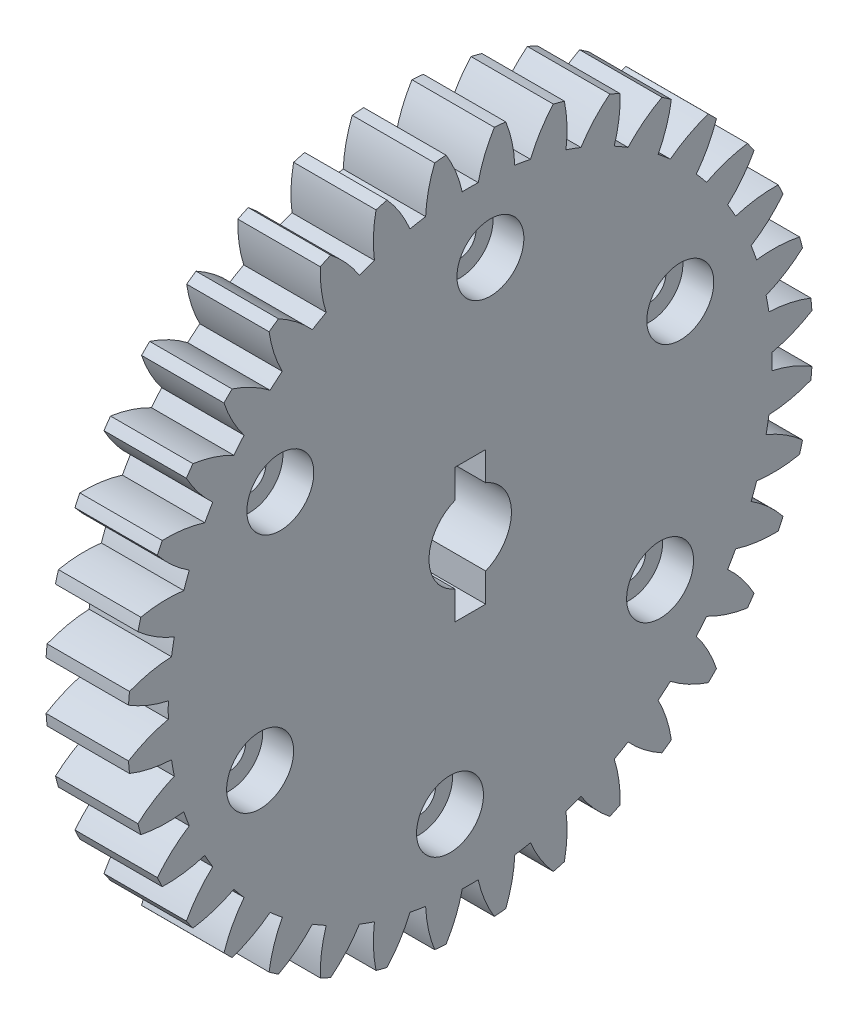
SolidWorks part; units mm, degrees
material "PLA personnalisé"
ref_plane "Plane1" through (0, 0, 0) normal (0, 0, 1) x (1, 0, 0)
ref_plane "Plane2" through (0, 0, 0) normal (0, 1, 0) x (1, 0, 0)
ref_plane "Plane3" through (0, 0, 0) normal (1, 0, 0) x (0, 0, -1)
other "Configuration Table"
sketch "HoldingSke" plane through (0, 0, 0) normal (0, 1, 0) x (1, 0, 0)
  line L0 (0, 0) -> (0.4623, -0.3359)
  line L1 (-15, 0) -> (100, 0) construction
  line L2 (0, 0) -> (-2.1039, 2.3779)
  line L3 (0, 0) -> (-11.863, 4.5341)
  line L4 (0, 0) -> (6.9867, 5.0761)
  line L5 (0, 0) -> (-46.8476, -17.4728)
  line L6 (0, 0) -> (-6.6317, -4.4744)
  line L7 (-2.1039, 2.3779) -> (8.6586, 51.2059)
  line L8 (-76.2, 54.61) -> (-74.8, 54.61)
  line L9 (-71.009, 38.7566) -> (-53.1078, 45.2721)
  line L10 (-76.2, 71.12) -> (104.1128, 71.12)
  line L11 (0, 0) -> (-8, 0)
  line L12 (-76.2, 101.6) -> (-76.147, 101.6)
  line L13 (24.9733, 27.94) -> (52.9518, 28.4284)
  line L14 (24.9733, 27.94) -> (24.9743, 27.94)
  line L15 (24.9733, 27.94) -> (100.4006, 29.5858)
  line L16 (-63.627, -1.75) -> (-12.827, -1.75)
  circle A0 centre (0, 0) radius 4
  circle A1 centre (0, 0) radius 29.3115
  circle A2 centre (0, 0) radius 37.5
  circle A3 centre (0, 0) radius 4
  dimension "MHD" = 58.623
  dimension "Hub_dia" = 75
  dimension "Bore" = 8
  dimension "MBD" = 8
  dimension "Num_teeth" = 36
  dimension "Pitch" = 0.5714
  dimension "Overall_len" = 50
  dimension "Show_teeth" = 36
  dimension "Thickness" = 8
  dimension "OAL" = 50.0001
  dimension "T_dim" = 1.4
  dimension "Ap" = 20
  dimension "H" = 19.05
  dimension "Pitch_radius" = 180.3128
  dimension "Width" = 8
  dimension "Backlash" = 0.053
  dimension "Addendum_fac" = 1
  dimension "Dedendum_fac" = 1.25
  dimension "Clearance_fac" = 0.25
  dimension "Dedendum_add" = 0.001
  dimension "Module" = 1.75
sketch "BasProSke" plane through (0, 0, 0) normal (0, 1, 0) x (1, 0, 0)
  line L0 (-10, 0) -> (60, 0) construction
  line L1 (0, 0) -> (0, 33.25)
  line L2 (0, 0) -> (8, 0)
  line L3 (8, 0) -> (8, 33.25)
  line L4 (8, 33.25) -> (0, 33.25)
  dimension "Thickness" = 8
  dimension "Diameter" = 66.5
revolve "Base-Revolve" add sketch "BasProSke" angle 360 about L0
sketch "TooCutSke" plane through (0, 0, 0) normal (1, 0, 0) x (0, 0, -1)
  line L1 (0, 0) -> (0, 107) construction
  line L2 (0, 0) -> (-1.4667, 31.4658) construction
  line L3 (0, 0) -> (-5.4863, 62.7083) construction
  line L4 (-1.4667, 31.4658) -> (-2.7431, 31.3542) construction
  arc A0 (0.7738, 29.3013) -> (-0.7738, 29.3013) centre (0, 0) ccw
  arc A1 (2.3593, 33.1917) -> (-2.3593, 33.1917) centre (0, 0) ccw
  circle A2 centre (0, 0) radius 31.5 construction
  circle A3 centre (0, 0) radius 29.6003 construction
  arc A4 (-0.7738, 29.3013) -> (-2.3593, 33.1917) centre (-13.0715, 26.5578) ccw
  arc A5 (2.3593, 33.1917) -> (0.7738, 29.3013) centre (13.0715, 26.5578) ccw
  dimension "Root_dia" = 58.623
  dimension "Overcut_dia" = 66.5508
  dimension "Pitch_dia" = 63
  dimension "Base_dia" = 59.2006
  dimension "Flank_rad" = 12.6
  dimension "Half_ang" = 5
  dimension "Half_CT" = 1.2813
extrude "ToothCut" cut sketch "TooCutSke" along normal through all
fillet "Breaks" [suppressed] radius 0.035 tangent propagation no
fillet "RootFillets" [suppressed] radius 0.4385
pattern_circular "TeethCuts" count 36 every 10 about axis through (-10, 0, 0) along (1, 0, 0) of "ToothCut", "RootFillets", "Breaks"
sketch "HubNeaOneSke" plane through (0, 0, 0) normal (-1, 0, 0) x (0, 0, 1)
  circle A0 centre (0, 0) radius 29.3115
  dimension "Diameter" = 58.623
extrude "HubNearOne" [suppressed] add sketch "HubNeaOneSke" along normal blind 42.0001
sketch "HubNeaBotSke" plane through (0, 0, 0) normal (-1, 0, 0) x (0, 0, 1)
  circle A0 centre (0, 0) radius 29.3115
  dimension "Diameter" = 58.623
extrude "HubNearBoth" [suppressed] add sketch "HubNeaBotSke" along normal blind 21
ref_plane "FarPln" through (8, 0, 0) normal (1, 0, 0) x (0, 0, -1)
sketch "HubFarSke" plane through (8, 0, 0) normal (1, 0, 0) x (0, 0, -1)
  circle A0 centre (0, 0) radius 29.3115
  dimension "Diameter" = 58.623
extrude "HubFar" [suppressed] add sketch "HubFarSke" along normal blind 21
sketch "BorSke" plane through (0, 0, 0) normal (1, 0, 0) x (0, 0, -1)
  circle A0 centre (0, 0) radius 4
  dimension "Diameter" = 8
extrude "Bore" cut sketch "BorSke" along normal mid plane 100.0001
sketch "KeySke" plane through (0, 0, 0) normal (1, 0, 0) x (0, 0, -1)
  line L0 (-1.5, 0) -> (-1.5, 5.4)
  line L1 (-1.5, 5.4) -> (1.5, 5.4)
  line L2 (1.5, 5.4) -> (1.5, 0)
  line L3 (0, 0) -> (0, 34) construction
  line L4 (-1.5, 0) -> (1.5, 0)
  dimension "Offset" = 5.4
  dimension "Width" = 3
extrude "Keyway" [suppressed] cut sketch "KeySke" along normal mid plane 100.0001
pattern_circular "Keyway2" [suppressed] count 2 every 90 about axis through (-10, 0, 0) along (1, 0, 0) reverse direction yes
sketch "Esquisse2" plane through (8, 0, 0) normal (1, 0, 0) x (0, 0, -1)
  line L0 (2.8979, 33.1235) -> (0, 0) construction
  line L1 (1.3673, 15.6288) -> (2.5547, 29.2)
  arc A0 (3.4508, 33.0704) -> (2.3442, 33.1673) centre (0, 0) ccw construction
  circle A1 centre (0, 0) radius 29.3115
  circle A2 centre (0, 0) radius 15.6885
  circle A3 centre (1.961, 22.4144) radius 1.6
  circle A4 centre (0, 0) radius 22.5
  dimension "D1" = 3.2
  dimension "D2" = 45
extrude "Enlèv. mat.-Extru.2" cut sketch "Esquisse2" against normal blind 10 contours A3
sketch "Esquisse3" plane through (8, 0, 0) normal (1, 0, 0) x (0, 0, -1)
  circle A0 centre (1.961, 22.4144) radius 3.25
  dimension "D1" = 6.5
extrude "Enlèv. mat.-Extru.3" cut sketch "Esquisse3" against normal blind 3
pattern_circular "Répétition circulaire1" count 6 over 360 about axis through (50.0001, 0, 0) along (-1, 0, 0) of "Enlèv. mat.-Extru.2", "Enlèv. mat.-Extru.3"
sketch "Esquisse4" plane through (8, 0, 0) normal (1, 0, 0) x (0, 0, -1)
  line L1 (1.5, -6.5) -> (-1.5, -6.5)
  line L2 (1.5, -6.5) -> (1.5, 6.5)
  line L3 (1.5, 6.5) -> (-1.5, 6.5)
  line L4 (-1.5, -6.5) -> (-1.5, 6.5)
  line L5 (1.5, -6.5) -> (-1.5, 6.5) construction
  line L6 (1.5, 6.5) -> (-1.5, -6.5) construction
  point P0 (0, 0)
  dimension "D1" = 13
  dimension "D2" = 3
extrude "Enlèv. mat.-Extru.4" cut sketch "Esquisse4" against normal blind 10
equation "' \"Module@HoldingSke\" = 6.35"
equation "' \"Num_teeth@HoldingSke\" = 12"
equation "' \"Ap@HoldingSke\" =  20"
equation "' \"Ap@HoldingSke\" = 20"
equation "' \"Width@HoldingSke\" = 0.5 * 25.4"
equation "' \"Hub_dia@HoldingSke\"= 1 * 25.4"
equation "' \"Hub_dia@HoldingSke\" = 1 * 25.4"
equation "' \"Overall_len@HoldingSke\" = 1.0 * 25.4"
equation "' \"Bore@HoldingSke\" = 0.75 * 25.4"
equation "' \"T_dim@HoldingSke\" = 0.1 * 25.4"
equation "' \"Width@KeySke\" = 0.25 * 25.4"
equation "' \"Show_teeth@HoldingSke\" = 13"
equation "' \"Backlash@HoldingSke\" = 0.009 * 25.4"
equation "' \"Addendum_fac@HoldingSke\" = 1.0"
equation "' \"Dedendum_fac@HoldingSke\" = 1.25"
equation "' \"Dedendum_add@HoldingSke\" = 0.00005 * 25.4"
equation "' \"Clearance_fac@HoldingSke\" = 0.25"
equation "\"Pitch@HoldingSke\" = 1 / \"Module@HoldingSke\""
equation "\"Overcut_dia@TooCutSke\" = (\"Num_teeth@HoldingSke\" + 2 * \"Addendum_fac@HoldingSke\") / \"Pitch@HoldingSke\" + 0.002 * 25.4"
equation "\"Pitch_dia@TooCutSke\" = \"Num_teeth@HoldingSke\" / \"Pitch@HoldingSke\""
equation "\"Base_dia@TooCutSke\" = \"Num_teeth@HoldingSke\" / \"Pitch@HoldingSke\" * cos((\"Ap@HoldingSke\"  * 3.14159265 / 180))"
equation "\"Root_dia@TooCutSke\" = (\"Num_teeth@HoldingSke\" + 2) / \"Pitch@HoldingSke\" - 2 * (\"Addendum_fac@HoldingSke\" + \"Dedendum_fac@HoldingSke\") / \"Pitch@HoldingSke\" - \"Dedendum_add@HoldingSke\" * 2"
equation "\"Half_ang@TooCutSke\" = 180 / \"Num_teeth@HoldingSke\""
equation "\"Half_CT@TooCutSke\" = \"Num_teeth@HoldingSke\" / \"Pitch@HoldingSke\" * sin((3.14159265 / 2 / \"Num_teeth@HoldingSke\")) / 2 - 7 * \"Backlash@HoldingSke\" / 4"
equation "\"Flank_rad@TooCutSke\" = \"Num_teeth@HoldingSke\" / \"Pitch@HoldingSke\" / 5"
equation "\"Radius@RootFillets\" = \"Clearance_fac@HoldingSke\" / \"Pitch@HoldingSke\" + \"Dedendum_add@HoldingSke\""
equation "\"Break_rad@Breaks\" = 0.02 / \"Pitch@HoldingSke\""
equation "\"Thickness@HoldingSke\" = \"Width@HoldingSke\""
equation "\"OAL@HoldingSke\" = \"Thickness@HoldingSke\""
equation "\"MHD@HoldingSke\" = (\"Num_teeth@HoldingSke\" + 2) / \"Pitch@HoldingSke\" - 2 * (\"Addendum_fac@HoldingSke\" + \"Dedendum_fac@HoldingSke\")  / \"Pitch@HoldingSke\" - \"Dedendum_add@HoldingSke\" * 2"
equation "\"MBD@HoldingSke\" = (\"Num_teeth@HoldingSke\" + 2) / \"Pitch@HoldingSke\" - 2 * (\"Addendum_fac@HoldingSke\" + \"Dedendum_fac@HoldingSke\")  / \"Pitch@HoldingSke\" - \"Dedendum_add@HoldingSke\" * 2 - 0.002 * 25.4"
equation "\"MHD@HoldingSke\" = ((sgn( \"MHD@HoldingSke\" - \"Hub_dia@HoldingSke\" )-1)*( \"MHD@HoldingSke\" - \"Hub_dia@HoldingSke\" ))/-2+ \"Hub_dia@HoldingSke\""
equation "\"MBD@HoldingSke\" = ((sgn( \"MBD@HoldingSke\" - \"Bore@HoldingSke\" )-1)*( \"MBD@HoldingSke\" - \"Bore@HoldingSke\" ))/-2+ \"Bore@HoldingSke\""
equation "\"OAL@HoldingSke\" = ((sgn( \"OAL@HoldingSke\" - \"Overall_len@HoldingSke\" )+1)*( \"OAL@HoldingSke\" - \"Overall_len@HoldingSke\" ))/2 + \"Overall_len@HoldingSke\" + 0.000002 * 25.4"
equation "\"Num_teeth@TeethCuts\" = int( \"Show_teeth@HoldingSke\" ) + 1"
equation "\"Num_teeth@TeethCuts\" = ((sgn( \"Num_teeth@TeethCuts\" - \"Num_teeth@HoldingSke\" )-1)*( \"Num_teeth@TeethCuts\" - \"Num_teeth@HoldingSke\" ))/-2+ \"Num_teeth@HoldingSke\""
equation "\"Num_teeth@TeethCuts\" = ((sgn( \"Num_teeth@TeethCuts\" - 2.0)+1)*( \"Num_teeth@TeethCuts\" - 2.0))/2 +2.0"
equation "\"Angle@TeethCuts\" = 360.0 / \"Num_teeth@HoldingSke\""
equation "\"Diameter@BasProSke\" = (\"Num_teeth@HoldingSke\" + 2 * \"Addendum_fac@HoldingSke\") / \"Pitch@HoldingSke\""
equation "\"Thickness@BasProSke\"  = \"Thickness@HoldingSke\""
equation "' \"Fillet_rad@BasProSke\" =  \"Thickness@HoldingSke\" * 0.05"
equation "' \"Fillet_rad@BasProSke\" = \"Thickness@HoldingSke\" * 0.05"
equation "\"MHD@HoldingSke\" = ((sgn( \"MHD@HoldingSke\" - \"Root_dia@TooCutSke\" )-1)*( \"MHD@HoldingSke\" - \"Root_dia@TooCutSke\" ))/-2+ \"Root_dia@TooCutSke\""
equation "\"Diameter@HubNeaOneSke\" = \"MHD@HoldingSke\""
equation "\"Length@HubNearOne\" = \"OAL@HoldingSke\" - \"Thickness@BasProSke\""
equation "\"Diameter@HubNeaBotSke\" = \"MHD@HoldingSke\""
equation "\"Length@HubNearBoth\" = ( \"OAL@HoldingSke\" - \"Thickness@BasProSke\" ) / 2.0"
equation "\"Thickness@FarPln\" = \"Thickness@BasProSke\""
equation "\"Diameter@HubFarSke\" = \"MHD@HoldingSke\""
equation "\"Length@HubFar\" = ( \"OAL@HoldingSke\" - \"Thickness@BasProSke\" ) / 2.0"
equation "\"Diameter@BorSke\" = \"MBD@HoldingSke\""
equation "\"D1@Bore\" = \"OAL@HoldingSke\" * 2.0"
equation "\"D1@Keyway\" = \"OAL@HoldingSke\" * 2.0"
equation "\"Offset@KeySke\" = \"T_dim@HoldingSke\" + \"MBD@HoldingSke\" / 2.0"
